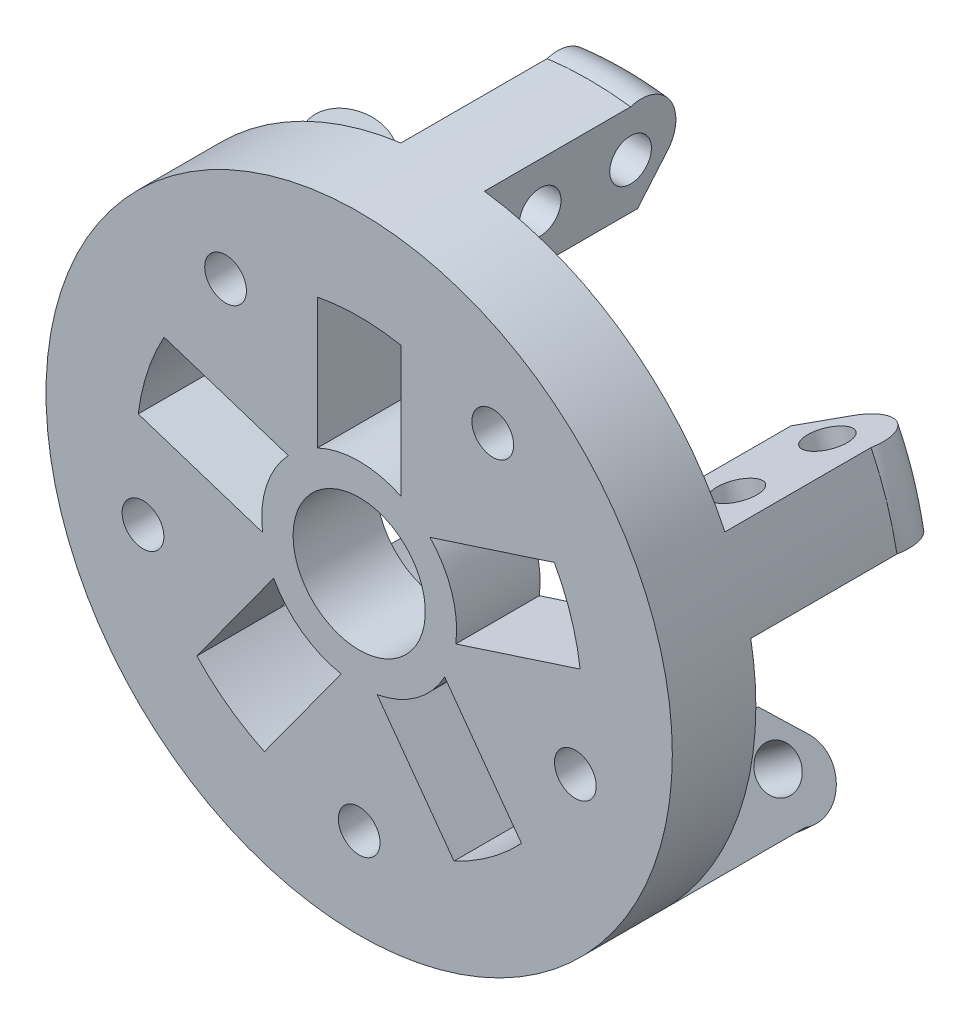
SolidWorks part; units mm, degrees
note: The reader was unsure of these and kept them because the rebuilt part matched: shared geometry of "草图7<3>".
ref_plane "前视基准面" through (0, 0, 0) normal (0, 0, 1) x (1, 0, 0)
ref_plane "上视基准面" through (0, 0, 0) normal (0, 1, 0) x (1, 0, 0)
ref_plane "右视基准面" through (0, 0, 0) normal (1, 0, 0) x (0, 0, -1)
other "Configuration Table"
sketch "草图1" plane through (0, 0, 0) normal (0, 1, 0) x (1, 0, 0)
  line L0 (0, 0) -> (0, 56.3655) construction
  line L1 (0, 0) -> (52.3594, 0) construction
  line L2 (0, 0) -> (-45, 0)
  line L3 (-45, 0) -> (-45, 12)
  line L4 (-45, 12) -> (-45, 33)
  line L5 (-36.9628, 38.2919) -> (-32, 34)
  line L6 (-32, 34) -> (-32, 12)
  line L7 (-32, 12) -> (0, 12)
  line L8 (0, 0) -> (0, 12)
  arc A0 (-45, 33) -> (-36.9628, 38.2919) centre (-40.2335, 34.51) cw
  point P9 (0, 0)
  point P13 (-37.9204, 40.2025)
  point P14 (-38.0884, 39.0265)
  dimension "D6" = 5
  dimension "D1" = 21
  dimension "D2" = 22
  dimension "D3" = 12
  dimension "D4" = 32
  dimension "D5" = 90
revolve "旋转1" add sketch "草图1" angle 360 about L0
sketch "草图2" plane through (0, 0, -12) normal (0, 0, -1) x (-1, 0, 0)
  line L0 (0, 0) -> (0, 47.1887) construction
  line L1 (0, 0) -> (44.8791, 14.5821) construction
  line L2 (0, 0) -> (27.7368, -38.1764) construction
  line L3 (0, 0) -> (-27.7368, -38.1764) construction
  line L4 (0, 0) -> (-44.8791, 14.5821) construction
  line L5 (0, 0) -> (0, 47.1887) construction
  line L6 (-6, 44.8338) -> (-6, 12.6491)
  line L7 (-40.7853, 19.5607) -> (-10.1759, 9.6151)
  line L8 (6, 44.8338) -> (6, 12.6491)
  line L9 (40.7853, 19.5607) -> (10.1759, 9.6151)
  line L10 (44.4935, 8.1481) -> (13.8841, -1.7975)
  line L11 (31.2067, -32.7446) -> (12.2891, -6.7066)
  line L12 (21.4985, -39.798) -> (2.5809, -13.7601)
  line L13 (-21.4985, -39.798) -> (-2.5809, -13.7601)
  line L14 (-31.2067, -32.7446) -> (-12.2891, -6.7066)
  line L15 (-44.4935, 8.1481) -> (-13.8841, -1.7975)
  line L16 (0, 0) -> (-6, 12.6491) construction
  arc A0 (-13.8841, -1.7975) -> (-12.2891, -6.7066) centre (0, 0) ccw
  circle A1 centre (0, 0) radius 45.2335 construction
  arc A2 (-6, 44.8338) -> (-40.7853, 19.5607) centre (0, 0) ccw
  arc A3 (-2.5809, -13.7601) -> (2.5809, -13.7601) centre (0, 0) ccw
  arc A4 (12.2891, -6.7066) -> (13.8841, -1.7975) centre (0, 0) ccw
  arc A5 (10.1759, 9.6151) -> (6, 12.6491) centre (0, 0) ccw
  arc A6 (-6, 12.6491) -> (-10.1759, 9.6151) centre (0, 0) ccw
  arc A7 (40.7853, 19.5607) -> (6, 44.8338) centre (0, 0) ccw
  arc A8 (31.2067, -32.7446) -> (44.4935, 8.1481) centre (0, 0) ccw
  arc A9 (-21.4985, -39.798) -> (21.4985, -39.798) centre (0, 0) ccw
  arc A10 (-44.4935, 8.1481) -> (-31.2067, -32.7446) centre (0, 0) ccw
  point P17 (0, 0)
  point P18 (0, 0)
  point P36 (0, 0)
  dimension "D3" = 28
  dimension "D2" = 47.1887
  dimension "D4" = 12
  dimension "D5" = 12
  dimension "D1" = 5
  dimension "D6" = 5
extrude "切除-拉伸2" cut sketch "草图2" along normal through all contours A9 L12 A3 L13 | L14 A0 L15 A10 | L10 A4 L11 A8 | L8 A5 L9 A7 | L6 A6 L7 A2
sketch "草图3" plane through (0, 0, -12) normal (0, 0, -1) x (-1, 0, 0)
  line L0 (0, 0) -> (0, -32) construction
  circle A0 centre (0, 0) radius 32 construction
  point P6 (0, -32)
  dimension "D1" = 64
hole_wizard "M1.6 六角圆柱头螺钉的柱形沉头孔1" positions "草图3" profile "草图4" counterbore size "M1.6" standard "GB" end condition up to next
sketch "草图4" plane through (0, -32, -12) normal (1, 0, 0) x (0, 1, 0)
  line L0 (0, 0) -> (0, 12)
  line L1 (0, 12) -> (3, 12)
  line L3 (3, 12) -> (3, 6)
  line L4 (3, 6) -> (6, 6)
  line L5 (6, 6) -> (6, 0)
  line L7 (6, 0) -> (0, 0)
  line L11 (0, -6.35) -> (0, 107.95) construction
  dimension "通孔孔直径" = 6
  dimension "通孔孔深度" = 12
  dimension "柱形沉头孔直径" = 12
  dimension "柱形沉头孔深度" = 6
pattern_circular "阵列(圆周)1" count 5 over 360 about axis through (0, 0.6622, 0) along (0, 0, 1) of "M1.6 六角圆柱头螺钉的柱形沉头孔1"
sketch "草图7" plane through (0, 0, -12) normal (0, 0, -1) x (-1, 0, 0)
  line L0 (-6, 31.4325) -> (-6, 12.6491)
  line L1 (6, 31.4325) -> (6, 12.6491)
  circle A0 centre (0, 0) radius 9.5
  circle A1 centre (0, 0) radius 14
  arc A2 (6, 31.4325) -> (-6, 31.4325) centre (0, 0) ccw construction
  arc A3 (6, 31.4325) -> (-6, 31.4325) centre (0, 0) ccw
  arc M16 (6, 31.4325) -> (-6, 31.4325) centre (0, 0) ccw
  dimension "D1" = 19
  dimension "D2" = 28
extrude "切除-拉伸3" cut sketch "草图7" against normal through all contours A0
extrude "切除-拉伸4" cut sketch "草图7<3>" against normal through all contours A1 L1 L0 M16
sketch "草图7<3>" plane through (0, 0, -12) normal (0, 0, -1) x (-1, 0, 0) same geometry as "草图7"
pattern_circular "阵列(圆周)2" count 5 over 360 about axis through (0, 0, 0) along (0, 0, 1) of "切除-拉伸4"
sketch "草图9" plane through (6, 0, 0) normal (1, 0, 0) x (0, 0, -1)
  line L0 (0, 0) -> (57.0729, 0) construction
  line L1 (0, 45) -> (0, -45) construction
  line L2 (12, 19.4879) -> (12, 44.5982) construction
  circle A0 centre (33, 38) radius 3
  circle A1 centre (20, 38) radius 3
  point P11 (0, 0)
  point P13 (18.9563, 39.1143)
  dimension "D1" = 6
  dimension "D2" = 21
  dimension "D3" = 20
  dimension "D4" = 38
extrude "切除-拉伸5" cut sketch "草图9" against normal through all
pattern_circular "阵列(圆周)3" count 5 over 360 of "切除-拉伸5"
